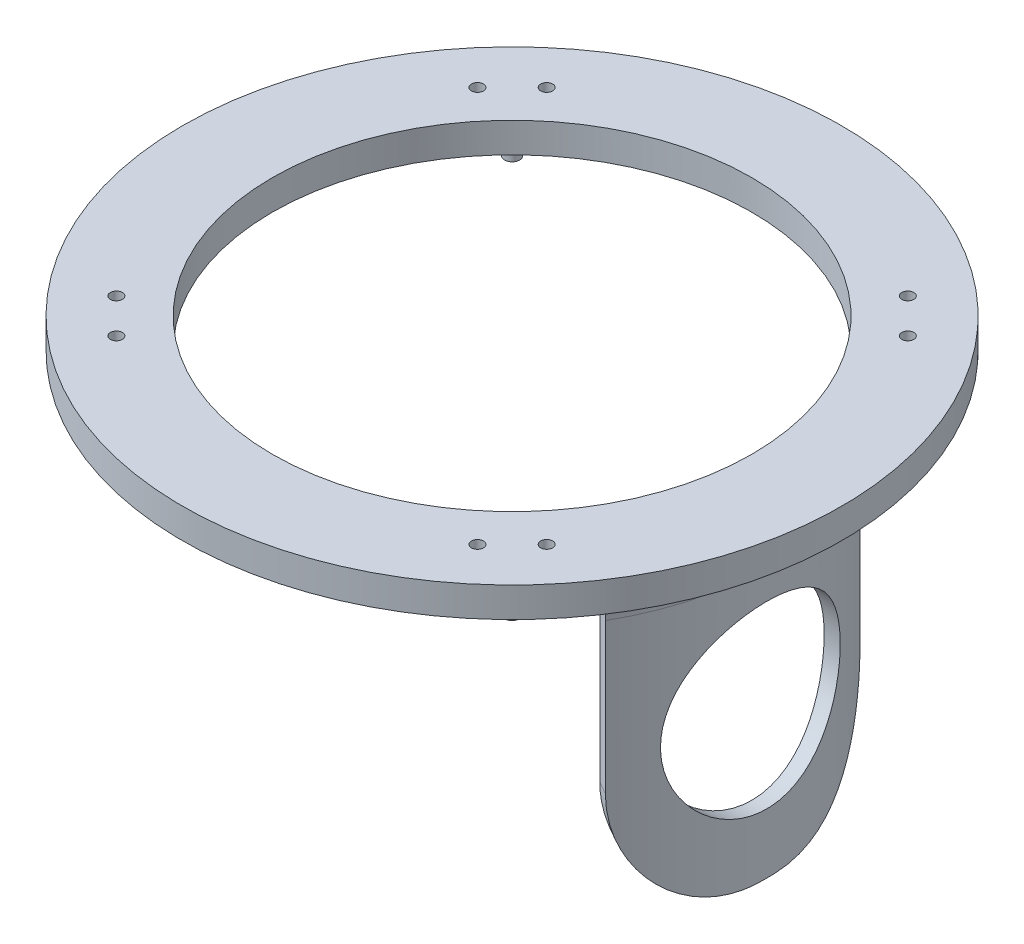
SolidWorks part; units mm, degrees
ref_plane "Front Plane" through (0, 0, 0) normal (0, 0, 1) x (1, 0, 0)
ref_plane "Top Plane" through (0, 0, 0) normal (0, 1, 0) x (1, 0, 0)
ref_plane "Right Plane" through (0, 0, 0) normal (1, 0, 0) x (0, 0, -1)
sketch "Sketch1" plane through (0, 0, 0) normal (0, 0, 1) x (1, 0, 0)
  line L0 (0, 1125.8152) -> (0, -48874.1848) construction
  line L1 (101.6, 1061.593) -> (107.95, 1061.593)
  line L2 (101.6, 1061.593) -> (101.6, 921.893)
  line L3 (101.6, 921.893) -> (107.95, 921.893)
  line L4 (107.95, 1061.593) -> (107.95, 921.893)
  line L5 (101.6, 909.193) -> (139.7, 909.193) construction
  line L6 (101.6, 909.193) -> (101.6, 921.893) construction
  line L7 (101.6, 921.893) -> (139.7, 921.893) construction
  line L8 (139.7, 909.193) -> (139.7, 921.893) construction
  line L9 (101.6, 1074.293) -> (139.7, 1074.293)
  line L10 (101.6, 1074.293) -> (101.6, 1061.593)
  line L11 (101.6, 1061.593) -> (139.7, 1061.593)
  line L12 (139.7, 1074.293) -> (139.7, 1061.593)
revolve "Revolve1" add sketch "Sketch1" angle 360 about L0 region at (120.65, 1067.943, 0) region at (104.775, 991.743, 0)
sketch "Sketch2" plane through (0, 0, 0) normal (0, 0, 1) x (1, 0, 0)
  line L0 (65.7096, 1023.493) -> (107.95, 1023.493)
  line L1 (107.95, 1023.493) -> (107.95, 985.393)
  line L2 (184.15, 985.393) -> (0, 985.393) construction
  line L3 (107.95, 985.393) -> (65.7096, 985.393)
  line L4 (65.7096, 985.393) -> (65.7096, 1023.493)
  line L5 (184.15, 985.393) -> (0, 985.393) construction
revolve "Cut-Revolve2" cut sketch "Sketch2" angle 360 about L5
sketch "Sketch4" plane through (0, 1074.293, 0) normal (0, -1, 0) x (1, 0, 0)
  line L0 (0, 0) -> (60.325, 104.486) construction
  line L1 (0, 0) -> (60.325, -104.486) construction
  line L2 (0, 0) -> (-120.65, 0) construction
  circle A0 centre (0, 0) radius 120.65 construction
  circle A1 centre (0, 0) radius 127
  circle A2 centre (0, 0) radius 114.3
  dimension "D1" = 120
  dimension "D2" = 120
  dimension "D3" = 6.35
  dimension "D4" = 6.35
sketch "Sketch5" plane through (0, 1061.593, 0) normal (0, -1, 0) x (1, 0, 0)
  line L0 (87.9882, 50.8) -> (93.4874, 53.975)
  line L1 (87.9882, -50.8) -> (93.4874, -53.975)
  line L2 (0, 0) -> (107.95, 0) construction
  circle A1 centre (0, 0) radius 107.95
  arc A2 (93.4874, -53.975) -> (93.4874, 53.975) centre (0, 0) ccw
  circle A5 centre (0, 0) radius 101.6
  arc A6 (87.9882, -50.8) -> (87.9882, 50.8) centre (0, 0) ccw
  point P6 (86.7016, 52.9659)
  dimension "D3" = 30
  dimension "D1" = 0
  dimension "D2" = 0
extrude "Cut-Extrude1" cut sketch "Sketch5" along normal through all flip side to cut
fillet "Fillet1" radius 25.4 1 edges at (107.95, 1061.593, 0)
fillet "Fillet3" radius 50.8 2 edges at (90.7378, 921.893, 52.3875) (90.7378, 921.893, -52.3875)
sketch "Sketch6" plane through (0, 1061.593, 0) normal (0, -1, 0) x (1, 0, 0)
  line L0 (-84.1899, -84.1899) -> (84.1899, 84.1899) construction
  line L1 (-84.1899, 84.1899) -> (84.1899, -84.1899) construction
  line L2 (0, 0) -> (0, 119.0625) construction
  circle A0 centre (0, 0) radius 119.0625 construction
  circle A1 centre (-84.1899, 84.1899) radius 3.175
  circle A2 centre (84.1899, 84.1899) radius 3.175
  circle A3 centre (84.1899, -84.1899) radius 3.175
  circle A4 centre (-84.1899, -84.1899) radius 3.175
  point P5 (0, 0)
  point P8 (0, 0)
  dimension "D2" = 238.125
  dimension "D3" = 6.35
  dimension "D1" = 45
extrude "Boss-Extrude1" add sketch "Sketch6" along normal blind 12.7
hole_wizard "1/4-20 Tapped Hole1" positions "Sketch9" profile "Sketch10" tap size "1/4-20" standard "ANSI Inch" end condition through all
sketch "Sketch9" plane through (0, 1061.593, 0) normal (0, -1, 0) x (-1, 0, 0)
  line L0 (0, 0) -> (84.1899, 84.1899) construction
  line L3 (0, 0) -> (76.5319, 91.2072) construction
  arc A0 (76.5319, 91.2072) -> (91.2072, 76.5319) centre (0, 0) cw
  point P0 (76.5319, 91.2072)
  point P2 (91.2072, 76.5319)
  dimension "D1" = 5
sketch "Sketch10" plane through (-76.5319, 1061.593, -91.2072) normal (1, 0, 0) x (0, 0, -1)
  line L0 (0, 0) -> (0, 12.7)
  line L1 (0, 12.7) -> (2.5527, 12.7)
  line L2 (2.5527, 12.7) -> (2.5527, 0)
  line L5 (2.5527, 0) -> (0, 0)
  line L11 (0, -6.35) -> (0, 107.95) construction
  dimension "Thru Tap Drill Dia." = 5.1054
  dimension "Thru Tap Drill Depth" = 12.7
cosmetic thread "Hole Thread1" parameters "D2"=6.35
cosmetic thread "Hole Thread2" parameters "D2"=6.35
pattern_circular "CirPattern1" count 4 over 360 about axis through (0, 1125.8152, 0) along (0, 1, 0) of "1/4-20 Tapped Hole1" reverse direction yes
